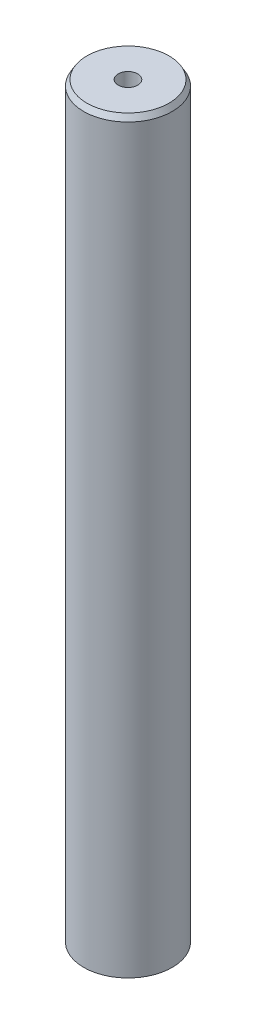
SolidWorks part; units mm, degrees
ref_plane "Front Plane" through (0, 0, 0) normal (0, 0, 1) x (1, 0, 0)
ref_plane "Top Plane" through (0, 0, 0) normal (0, 1, 0) x (1, 0, 0)
ref_plane "Right Plane" through (0, 0, 0) normal (1, 0, 0) x (0, 0, -1)
sketch "Sketch1" plane through (0, 0, 0) normal (0, 1, 0) x (1, 0, 0)
  circle A0 centre (0, 0) radius 5
  dimension "SHAFT_OD" = 10
extrude "Boss-Extrude1" add sketch "Sketch1" along normal blind 84.7232
sketch "Sketch2" plane through (0, 0, 0) normal (0, 1, 0) x (1, 0, 0)
  circle A0 centre (0, 0) radius 1.1064
  dimension "BORE_D" = 2.2127
extrude "Cut-Extrude1" cut sketch "Sketch2" along normal through all
chamfer "Chamfer1" distance 0.6294 angle 30 2 edges at (0, 84.7232, 5) (0, 0, 5) first distance on face at (0, 84.7232, 5) first distance on face at (0, 0, 1.1064)
